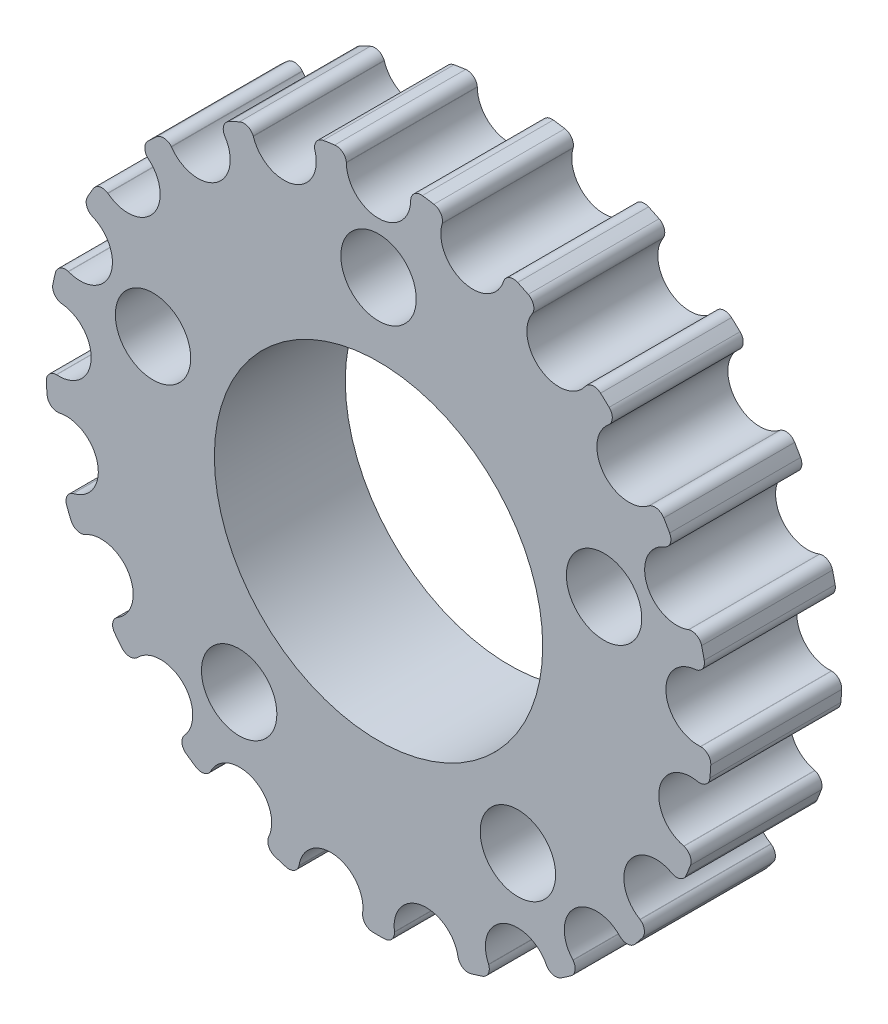
SolidWorks part; units mm, degrees
material "6061-T6 (SS)"
ref_plane "Front Plane" through (0, 0, 0) normal (0, 0, 1) x (1, 0, 0)
ref_plane "Top Plane" through (0, 0, 0) normal (0, 1, 0) x (1, 0, 0)
ref_plane "Right Plane" through (0, 0, 0) normal (1, 0, 0) x (0, 0, -1)
sketch "Pitch diameter" plane through (0, 0, 0) normal (0, 0, 1) x (1, 0, 0)
  circle A0 centre (0, 0) radius 16.7113 construction
  dimension "D1" = 33.4225
sketch "Sketch2" plane through (0, 0, 0) normal (0, 0, 1) x (1, 0, 0)
  circle A0 centre (0, 0) radius 16.1398
  dimension "D1" = 32.2795
extrude "Boss-Extrude1" add sketch "Sketch2" along normal blind 6.35
sketch "Sketch3" plane through (0, 0, 0) normal (0, 0, -1) x (-1, 0, 0)
  line L0 (-1.6121, 16.0591) -> (-1.56, 15.5398)
  line L1 (1.6121, 16.0591) -> (1.56, 15.5398)
  line L2 (-1.56, 15.5398) -> (1.56, 15.5398) construction
  circle A0 centre (0, 0) radius 16.1398 construction
  arc A1 (-1.56, 15.5398) -> (1.56, 15.5398) centre (0, 15.5398) ccw
  circle A2 centre (0, 0) radius 16.1398 construction
  arc A3 (1.6121, 16.0591) -> (-1.6121, 16.0591) centre (0, 0) ccw
  point P10 (0, 15.5398)
  point P15 (0, 13.9798)
  point P16 (0, 16.1398)
  dimension "D1" = 1.56
  dimension "D2" = 2.16
extrude "Cut-Extrude1" cut sketch "Sketch3" against normal through all
fillet "Fillet1" radius 0.5 2 edges at (-1.6121, 16.0591, 3.175) (1.6121, 16.0591, 3.175)
pattern_circular "CirPattern1" count 21 over 360 about axis through (0, 0, 0) along (0, 0, 1) of "Cut-Extrude1", "Fillet1"
sketch "Sketch4" plane through (0, 0, 6.35) normal (0, 0, 1) x (1, 0, 0)
  circle A0 centre (0, 0) radius 7.9629
  dimension "D1" = 15.9258
extrude "Cut-Extrude2" cut sketch "Sketch4" against normal through all
sketch "Sketch5" plane through (0, 0, 6.35) normal (0, 0, 1) x (1, 0, 0)
  line L0 (0, 0) -> (0, 11.5)
  point P0 (0, 0)
  point P7 (0, 0)
  dimension "D1" = 11.5
hole_wizard "#6 Clearance Hole1" positions "Sketch9" profile "Sketch10" hole size "#6" standard "ANSI Inch" end condition through all
sketch "Sketch9" plane through (0, 0, 6.35) normal (0, 0, 1) x (1, 0, 0)
  point P0 (0, 11.5)
sketch "Sketch10" plane through (0, 11.5, 6.35) normal (1, 0, 0) x (0, -1, 0)
  line L0 (0, 0) -> (0, 6.35)
  line L1 (0, 6.35) -> (1.8288, 6.35)
  line L2 (1.8288, 6.35) -> (1.8288, 0)
  line L5 (1.8288, 0) -> (0, 0)
  line L11 (0, -6.35) -> (0, 107.95) construction
  dimension "Thru Hole Dia." = 3.6576
  dimension "Thru Hole Depth" = 6.35
pattern_circular "CirPattern2" count 5 over 360 about axis through (0, 0, 6.35) along (0, 0, 1) of "#6 Clearance Hole1"
equation "\"NumberOfTeeth\"= 21"
equation "\"Pitch\"= 5mm"
equation "\"PitchDiameter\"= ( \"Pitch\" * \"NumberOfTeeth\" ) / Pi"
equation "\"OD\"= \"PitchDiameter\" - 0.0225in * 2"
equation "\"D1@Pitch diameter\" = \"PitchDiameter\""
equation "\"D1@Sketch2\"=\"OD\""
equation "\"D1@CirPattern1\"=\"NumberOfTeeth\""
